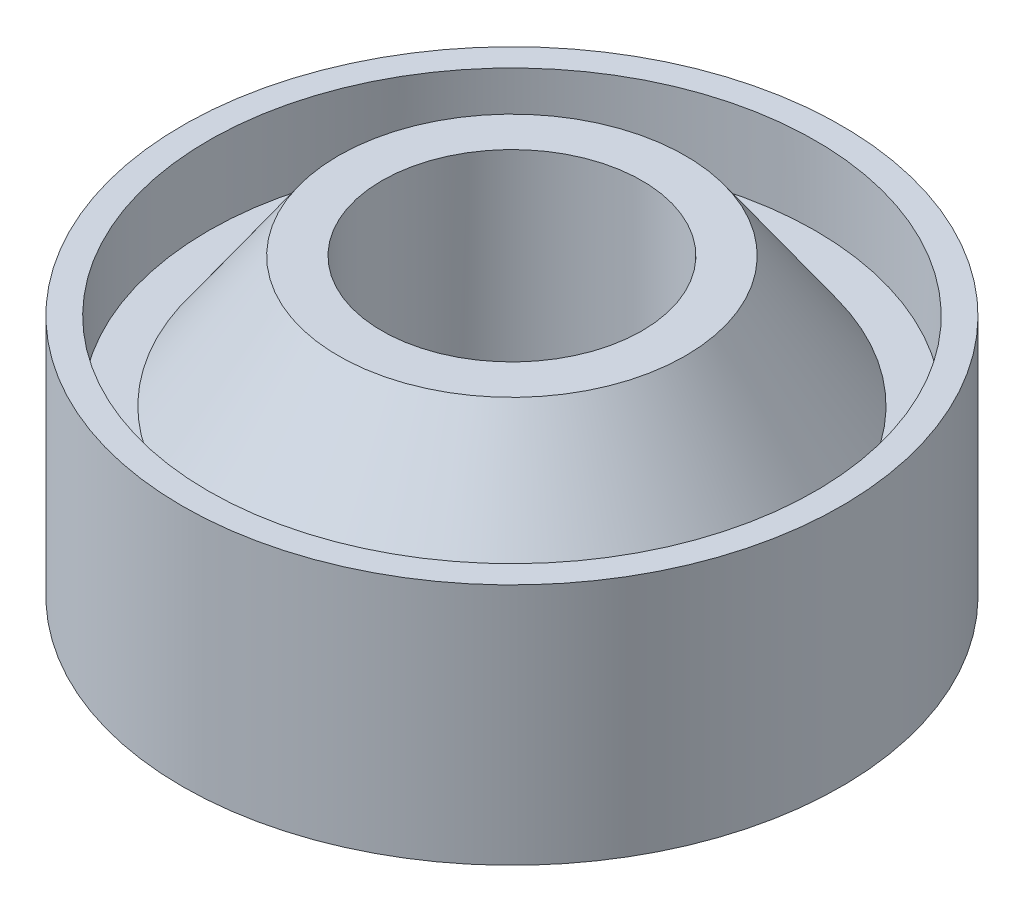
SolidWorks part; units mm, degrees
ref_plane "Front Plane" through (0, 0, 0) normal (0, 0, 1) x (1, 0, 0)
ref_plane "Top Plane" through (0, 0, 0) normal (0, 1, 0) x (1, 0, 0)
ref_plane "Right Plane" through (0, 0, 0) normal (1, 0, 0) x (0, 0, -1)
sketch "Sketch1" plane through (0, 0, 0) normal (0, 1, 0) x (1, 0, 0)
  circle A0 centre (0, 0) radius 38
  circle A1 centre (0, 0) radius 35
  dimension "D1" = 76
  dimension "D2" = 70
extrude "Boss-Extrude1" add sketch "Sketch1" along normal blind 14 and the other way blind 14
ref_plane "Plane1" through (0, 0, 0) normal (0, -1, 0) x (-1, 0, 0)
sketch "Sketch2" plane through (0, 0, 0) normal (0, -1, 0) x (-1, 0, 0)
  circle A0 centre (0, 0) radius 35
extrude "Boss-Extrude2" add sketch "Sketch2" along normal blind 5 and the other way blind 5
sketch "Sketch5" plane through (0, 5, 0) normal (0, 1, 0) x (1, 0, 0)
  circle A0 centre (0, 0) radius 20
  circle A1 centre (0, 0) radius 15
  dimension "D1" = 40
  dimension "D2" = 30
extrude "Boss-Extrude3" add sketch "Sketch5" along normal blind 15
sketch "Sketch6" plane through (0, -5, 0) normal (0, -1, 0) x (1, 0, 0)
  circle A0 centre (0, 0) radius 20
  circle A1 centre (0, 0) radius 15
  dimension "D1" = 40
  dimension "D2" = 30
extrude "Boss-Extrude4" add sketch "Sketch6" along normal blind 15
draft "Draft2" type of draft neutral plane draft angle 35 faces to draft 1 face at (-20, 20, 0) neutral plane through (0, 20, 0) neutral plane normal (0, 1, 0) parameters "D1"=35
draft "Draft3" type of draft neutral plane draft angle 35 faces to draft 1 face at (20, -20, 0) neutral plane through (0, -20, 0) neutral plane normal (0, -1, 0) parameters "D1"=35
sketch "Sketch14" plane through (0, -5, 0) normal (0, -1, 0) x (1, 0, 0)
  circle A0 centre (0, 0) radius 12
  dimension "D1" = 24
extrude "Cut-Extrude3" cut sketch "Sketch14" against normal blind 15
sketch "Sketch15" plane through (0, 5, 0) normal (0, 1, 0) x (1, 0, 0)
  circle A0 centre (0, 0) radius 15
extrude "Cut-Extrude4" cut sketch "Sketch15" against normal mid plane 67
